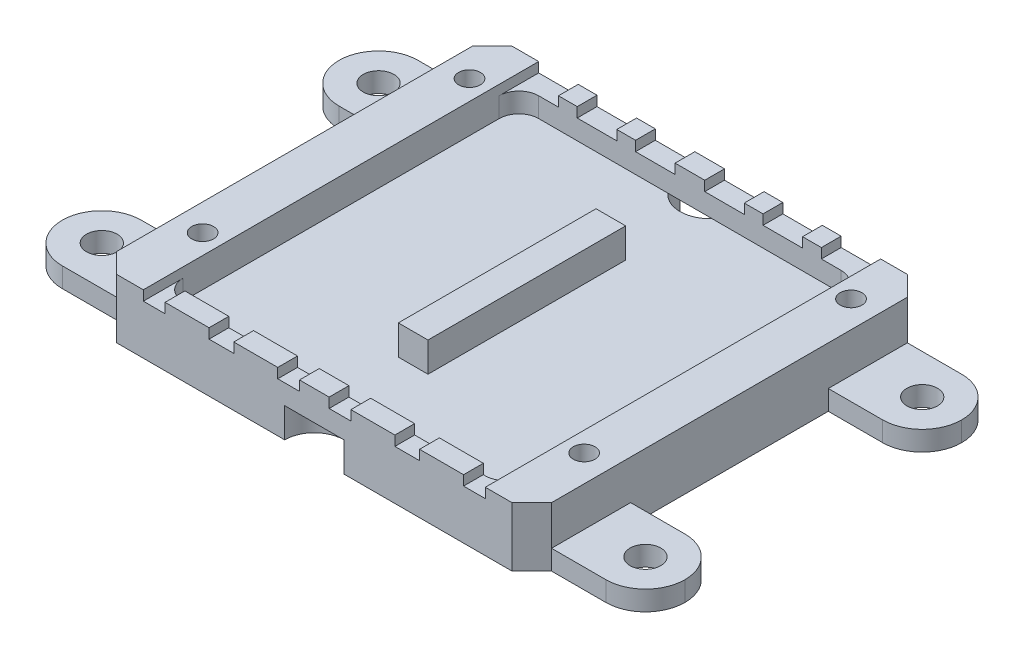
SolidWorks part; units mm, degrees
ref_plane "前视基准面" through (0, 0, 0) normal (0, 0, 1) x (1, 0, 0)
ref_plane "上视基准面" through (0, 0, 0) normal (0, 1, 0) x (1, 0, 0)
ref_plane "右视基准面" through (0, 0, 0) normal (1, 0, 0) x (0, 0, -1)
sketch "草图1" plane through (0, 0, 0) normal (0, 1, 0) x (1, 0, 0)
  line L0 (-27.5, 14) -> (27.5, 14) construction
  line L1 (22, -20) -> (-22, -20)
  line L2 (22, -20) -> (22, 20)
  line L3 (22, 20) -> (-22, 20)
  line L4 (-22, -20) -> (-22, 20)
  line L5 (22, -20) -> (-22, 20) construction
  line L6 (22, 20) -> (-22, -20) construction
  line L7 (-22, 18) -> (-31.5, 18)
  line L8 (-22, 18) -> (-22, 10)
  line L9 (-22, 10) -> (-31.5, 10)
  line L10 (-31.5, 18) -> (-31.5, 10)
  line L11 (-22, -10) -> (-31.5, -10)
  line L12 (-22, -10) -> (-22, -18)
  line L13 (-22, -18) -> (-31.5, -18)
  line L14 (-31.5, -10) -> (-31.5, -18)
  line L15 (22, 18) -> (31.5, 18)
  line L16 (22, 18) -> (22, 10)
  line L17 (22, 10) -> (31.5, 10)
  line L18 (31.5, 18) -> (31.5, 10)
  line L19 (22, -10) -> (31.5, -10)
  line L20 (22, -10) -> (22, -18)
  line L21 (22, -18) -> (31.5, -18)
  line L22 (31.5, -10) -> (31.5, -18)
  line L23 (27.5, 14) -> (27.5, -14) construction
  line L24 (27.5, -14) -> (-27.5, -14) construction
  line L25 (-27.5, -14) -> (-27.5, 14) construction
  line L26 (0, -14) -> (0, 0) construction
  line L27 (31.5, 14) -> (27.5, 14) construction
  line L28 (31.5, -14) -> (27.5, -14) construction
  line L29 (-31.5, 14) -> (-27.5, 14) construction
  line L30 (-31.5, -14) -> (-27.5, -14) construction
  line L31 (-27.5, 0) -> (0, 0) construction
  circle A0 centre (-27.5, 14) radius 1.55
  circle A1 centre (-27.5, -14) radius 1.55
  circle A2 centre (27.5, 14) radius 1.55
  circle A3 centre (27.5, -14) radius 1.55
  point P0 (0, 0)
  point P37 (-22, 20)
  point P38 (-22, -9)
  dimension "D6" = 3.1
  dimension "D3" = 28
  dimension "D1" = 44
  dimension "D2" = 40
  dimension "D4" = 55
  dimension "D5" = 8
  dimension "D7" = 4
extrude "凸台-拉伸1" add sketch "草图1" along normal blind 2 contours L4 L1 L2 L3 | L7 L10 L9 L4 A0 | L11 L14 L13 L4 A1 | L22 L19 L2 L21 A3 | L18 L15 L2 L17 A2 region at (0, 0, 0) region at (22.1242, 0, 14) region at (-26.75, 0, 17.8758) region at (22.1242, 0, -14) region at (-26.75, 0, -10.1242)
sketch "草图2" plane through (0, 2, 0) normal (0, 1, 0) x (1, 0, 0)
  line L4 (22, -20) -> (22, 20)
  line L5 (-22, -20) -> (22, -20)
  line L6 (-22, 20) -> (-22, -20)
  line L7 (22, 20) -> (-22, 20)
  line L10 (22, -20) -> (-22, -20) construction
  line L11 (22, -10) -> (22, 10) construction
  line L12 (22, 20) -> (-22, 20) construction
  line L13 (-22, -10) -> (-22, 10) construction
extrude "凸台-拉伸2" add sketch "草图2" along normal blind 4
fillet "圆角3" radius 4 8 edges at (31.5, 1, -18) (31.5, 1, -10) (31.5, 1, 10) (31.5, 1, 18) (-31.5, 1, 18) (-31.5, 1, 10) (-31.5, 1, -18) (-31.5, 1, -10)
sketch "草图3" plane through (0, 6, 0) normal (0, 1, 0) x (1, 0, 0)
  line L0 (-27.5525, 0) -> (27.6913, 0) construction
  line L1 (0, 25.4358) -> (0, -26.8932) construction
  line L2 (-1.5, 10) -> (-1.5, -10)
  line L3 (1.5, 10) -> (1.5, -10)
  line L15 (17.3, 18) -> (17.3, -18)
  line L16 (-17.3, 18) -> (-17.3, -18)
  line L20 (-22, -18) -> (22, -18)
  line L21 (-17.3, -18) -> (17.3, -18)
  line L22 (-17.3, 25.4358) -> (-17.3, -26.8932) construction
  line L23 (22, 18) -> (-22, 18)
  line L24 (17.3, 18) -> (-17.3, 18)
  line L25 (17.3, 25.4358) -> (17.3, -26.8932) construction
  line L26 (-1.5, -10) -> (1.5, -10)
  line L27 (-1.5, 10) -> (1.5, 10)
  line L28 (-27.5525, 10) -> (27.6913, 10) construction
  line L29 (-1.5, 25.4358) -> (-1.5, -26.8932) construction
  line L30 (-27.5525, -10) -> (27.6913, -10) construction
  line L31 (1.5, 25.4358) -> (1.5, -26.8932) construction
  dimension "D5" = 2
  dimension "D1" = 1.5
  dimension "D2" = 1.5
  dimension "D3" = 15.8
  dimension "D4" = 15.8
  dimension "D6" = 2
  dimension "D7" = 10
  dimension "D8" = 10
extrude "切除-拉伸1" cut sketch "草图3" against normal blind 3
sketch "草图4" plane through (0, 6, 0) normal (0, 1, 0) x (1, 0, 0)
  line L0 (-27.4831, 0) -> (27.2055, 0) construction
  line L1 (0, 25.5746) -> (0, -24.6723) construction
  line L2 (17.3, -18) -> (17.3, 18) construction
  line L3 (-17.3, 18) -> (-17.3, -18) construction
  line L4 (17.3, -20) -> (17.3, -18)
  line L5 (-17.3, 20) -> (-17.3, 18)
  line L6 (22, 20) -> (-22, 20) construction
  line L7 (-22, -20) -> (22, -20) construction
  line L8 (17.3, 20) -> (13.3, 20)
  line L9 (-17.3, -20) -> (-15.1, -20)
  line L10 (-13.3, 20) -> (-13.3, 18)
  line L11 (13.3, 18) -> (13.3, 20)
  line L12 (13.3, -18) -> (13.3, 20) construction
  line L13 (-13.3, 20) -> (-13.3, -18) construction
  line L14 (17.3, 18) -> (-17.3, 18) construction
  line L15 (17.3, 18) -> (13.3, 18)
  line L16 (-17.3, -18) -> (-17.3, -20)
  line L17 (-17.3, 20) -> (-17.3, -18) construction
  line L18 (17.3, 18) -> (17.3, 20)
  line L19 (17.3, -18) -> (17.3, 20) construction
  line L21 (-1.5, 10) -> (-1.5, -10) construction
  line L22 (1.5, -10) -> (1.5, 10) construction
  line L23 (-1.5, 20) -> (-1.5, 18)
  line L24 (5.5, 18) -> (5.5, 20)
  line L25 (-5.5, 20) -> (-5.5, 18)
  line L26 (1.5, -10) -> (1.5, 10) construction
  line L27 (-5.5, 20) -> (-5.5, -10) construction
  line L28 (-1.5, 20) -> (-5.5, 20)
  line L29 (-1.5, 18) -> (-5.5, 18)
  line L30 (1.5, 18) -> (1.5, 20)
  line L31 (-1.5, 10) -> (-1.5, -10) construction
  line L33 (-1.5, 20) -> (-1.5, -10) construction
  line L34 (1.5, -20) -> (3.7, -20)
  line L35 (1.5, -18) -> (3.7, -18)
  line L36 (-9.4, 25.5746) -> (-9.4, -24.6723) construction
  line L37 (9.4, 25.5746) -> (9.4, -24.6723) construction
  line L38 (7.4, 20) -> (7.4, 18)
  line L39 (11.4, 20) -> (11.4, 18)
  line L40 (-7.4, 20) -> (-7.4, 18)
  line L41 (-11.4, 20) -> (-11.4, 18)
  line L42 (-13.3, 20) -> (-17.3, 20)
  line L43 (-13.3, 18) -> (-17.3, 18)
  line L44 (-7.4, 20) -> (-11.4, 20)
  line L45 (-7.4, 18) -> (-11.4, 18)
  line L46 (5.5, 20) -> (1.5, 20)
  line L47 (5.5, 18) -> (1.5, 18)
  line L48 (11.4, 20) -> (7.4, 20)
  line L49 (11.4, 18) -> (7.4, 18)
  line L50 (-11.4, 25.5746) -> (-11.4, -24.6723) construction
  line L51 (-7.4, 25.5746) -> (-7.4, -24.6723) construction
  line L52 (7.4, 25.5746) -> (7.4, -24.6723) construction
  line L53 (11.4, 25.5746) -> (11.4, -24.6723) construction
  line L54 (-17.3, -18) -> (17.3, -18) construction
  line L55 (-17.3, -18) -> (-15.1, -18)
  line L56 (-15.1, -18) -> (-15.1, -20)
  line L57 (15.1, -20) -> (15.1, -18)
  line L58 (1.5, -18) -> (1.5, -20)
  line L59 (-1.5, -18) -> (-1.5, -20)
  line L60 (-3.7, -18) -> (-3.7, -20)
  line L61 (3.7, -18) -> (3.7, -20)
  line L62 (-10.65, -18) -> (-10.65, -20)
  line L63 (-8.15, -18) -> (-8.15, -20)
  line L64 (8.15, -18) -> (8.15, -20)
  line L65 (10.65, -18) -> (10.65, -20)
  line L66 (8.15, -18) -> (10.65, -18)
  line L67 (8.15, -20) -> (10.65, -20)
  line L68 (15.1, -18) -> (17.3, -18)
  line L69 (15.1, -20) -> (17.3, -20)
  line L70 (-3.7, -18) -> (-1.5, -18)
  line L71 (-3.7, -20) -> (-1.5, -20)
  line L72 (-10.65, -18) -> (-8.15, -18)
  line L73 (-10.65, -20) -> (-8.15, -20)
  line L74 (-10.65, 25.5746) -> (-10.65, -24.6723) construction
  line L75 (-8.15, 25.5746) -> (-8.15, -24.6723) construction
  line L76 (8.15, 25.5746) -> (8.15, -24.6723) construction
  line L77 (10.65, 25.5746) -> (10.65, -24.6723) construction
  dimension "D5" = 9.4
  dimension "D11" = 2.2
  dimension "D3" = 2
  dimension "D19" = 4
  dimension "D1" = 4
  dimension "D2" = 4
  dimension "D4" = 4
  dimension "D6" = 9.4
  dimension "D7" = 2
  dimension "D8" = 2
  dimension "D9" = 2
  dimension "D10" = 2
  dimension "D12" = 2.2
  dimension "D13" = 2.2
  dimension "D14" = 2.2
  dimension "D15" = 1.25
  dimension "D16" = 1.25
  dimension "D17" = 1.25
  dimension "D18" = 1.25
extrude "切除-拉伸2" cut sketch "草图4" against normal blind 1
fillet "圆角2" radius 2 4 edges at (17.3, 4, -18) (-17.3, 4, -18) (-17.3, 4, 18) (17.3, 4, 18)
sketch "草图5" plane through (0, 6, 0) normal (0, 1, 0) x (1, 0, 0)
  line L0 (-29.4032, 0) -> (28.1262, 0) construction
  line L1 (0, 28.1432) -> (0, -32.3448) construction
  line L8 (-22, 20) -> (-22, -20) construction
  line L9 (22, -20) -> (22, 20) construction
  circle A0 centre (19.3, 15) radius 1.1
  circle A1 centre (19.3, -12) radius 1.1
  circle A2 centre (-19.3, -12) radius 1.1
  circle A3 centre (-19.3, 15) radius 1.1
  dimension "D1" = 2.2
  dimension "D2" = 2.7
  dimension "D3" = 2.7
  dimension "D4" = 15
  dimension "D5" = 12
extrude "切除-拉伸3" cut sketch "草图5" against normal through all
sketch "草图6" plane through (0, 0, 0) normal (0, -1, 0) x (1, 0, 0)
  circle A0 centre (19.3, 12) radius 2
  circle A1 centre (-19.3, 12) radius 2
  circle A2 centre (-19.3, -15) radius 2
  circle A3 centre (19.3, -15) radius 2
  dimension "D1" = 4
extrude "切除-拉伸4" cut sketch "草图6" against normal blind 2.5
chamfer "Chamfer3" distance 2 angle 45 4 edges at (-22, 3, -20) (22, 3, -20) (22, 3, 20) (-22, 3, 20)
sketch "Sketch1" plane through (0, 0, 0) normal (0, -1, 0) x (1, 0, 0)
  line L0 (0, 0) -> (0, -20) construction
  line L1 (0, 0) -> (0, 20) construction
  line L3 (20, 20) -> (-20, 20) construction
  circle A0 centre (0, -20) radius 3
  circle A1 centre (0, 20) radius 3
  point P5 (0, 20)
  point P8 (0, 20)
extrude "Cut-Extrude1" cut sketch "Sketch1" against normal blind 3
